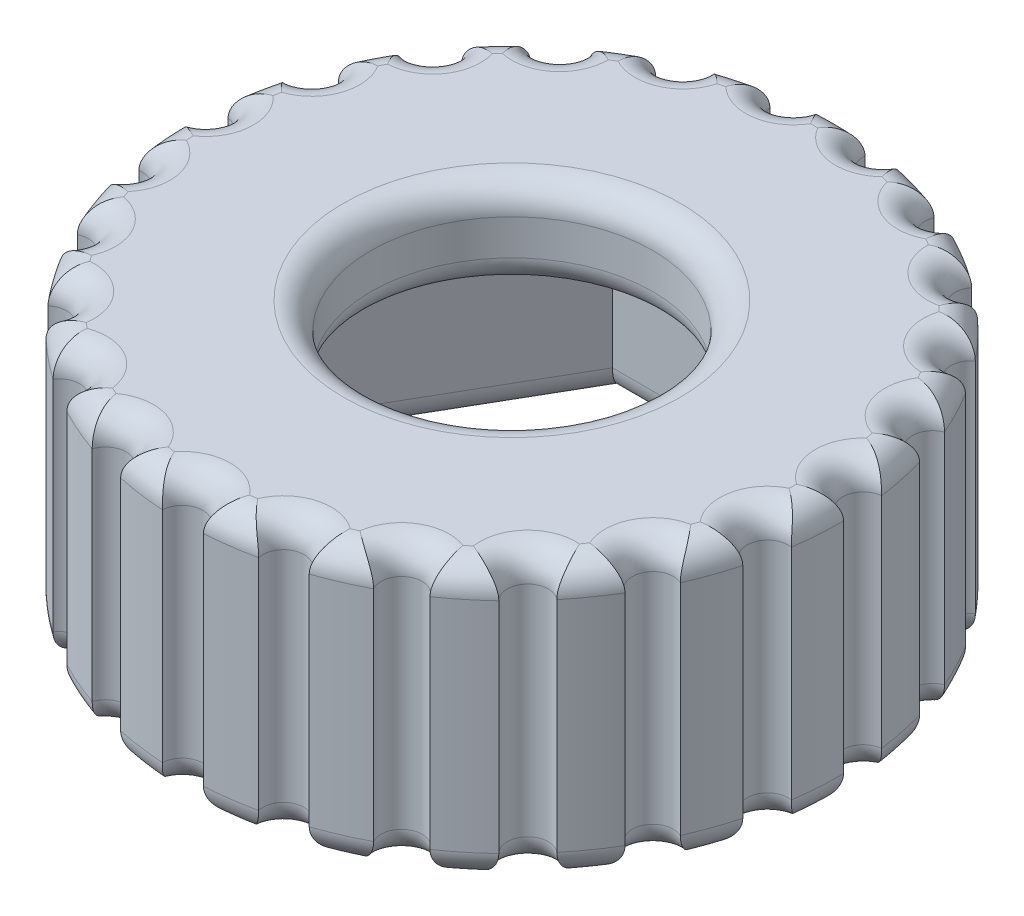
SolidWorks part; units mm, degrees
ref_plane "Front Plane" through (0, 0, 0) normal (0, 0, 1) x (1, 0, 0)
ref_plane "Top Plane" through (0, 0, 0) normal (0, 1, 0) x (1, 0, 0)
ref_plane "Right Plane" through (0, 0, 0) normal (1, 0, 0) x (0, 0, -1)
sketch "Sketch1" plane through (0, 0, 0) normal (0, 1, 0) x (1, 0, 0)
  line L0 (10.0459, 0) -> (5.0229, 8.7)
  line L1 (5.0229, 8.7) -> (-5.0229, 8.7)
  line L2 (-5.0229, 8.7) -> (-10.0459, 0)
  line L3 (-10.0459, 0) -> (-5.0229, -8.7)
  line L4 (-5.0229, -8.7) -> (5.0229, -8.7)
  line L5 (5.0229, -8.7) -> (10.0459, 0)
  line L6 (9.815, 0) -> (4.9075, 8.5) construction
  line L7 (4.9075, 8.5) -> (-4.9075, 8.5) construction
  line L8 (-4.9075, 8.5) -> (-9.815, 0) construction
  line L9 (-9.815, 0) -> (-4.9075, -8.5) construction
  line L10 (-4.9075, -8.5) -> (4.9075, -8.5) construction
  line L11 (4.9075, -8.5) -> (9.815, 0) construction
  circle A0 centre (0, 0) radius 10.0459 construction
  circle A1 centre (0, 0) radius 12.0459
extrude "Boss-Extrude1" add sketch "Sketch1" along normal blind 10
sketch "Sketch2" plane through (0, 10, 0) normal (0, 1, 0) x (1, 0, 0)
  circle A0 centre (0, 0) radius 5 construction
  circle A1 centre (0, 0) radius 12.0459
  circle A2 centre (0, 0) radius 12.0459
  circle A3 centre (0, 0) radius 5.15
  dimension "D2" = 10
  dimension "D1" = 0
  dimension "D3" = 0.15
extrude "Boss-Extrude2" add sketch "Sketch2" against normal blind 3.3
fillet "Fillet1" radius 1 7 edges at (0, 6.7, 5.15) (7.5344, 6.7, -4.35) (0, 6.7, -8.7) (-7.5344, 6.7, -4.35) (-7.5344, 6.7, 4.35) (0, 6.7, 8.7) (7.5344, 6.7, 4.35)
sketch "Sketch3" plane through (0, 0, 0) normal (0, -1, 0) x (1, 0, 0)
  circle A0 centre (0, 12.0459) radius 0.75
  circle A1 centre (0, 0) radius 12.0459 construction
  point P4 (0, 0)
  dimension "D1" = 1.5
extrude "Cut-Extrude1" cut sketch "Sketch3" against normal through all both and the other way through all
pattern_circular "CirPattern1" count 23 over 360 about axis through (0, 0, 0) along (0, 1, 0) of "Cut-Extrude1"
fillet "Fillet2" radius 1 99 edges at (0, 10, 5.15) (-10.6437, 10, -3.7828) (-9.2284, 10, -6.5141) (-7.1287, 10, -8.7624) (-4.5003, 10, -10.3607) (-1.5381, 10, -11.1907) (1.5381, 10, -11.1907) (4.5003, 10, -10.3607) (7.1287, 10, -8.7624) (9.2284, 10, -6.5141) (10.6437, 10, -3.7828) (11.2696, 10, -0.7709) (11.0596, 10, 2.2982) (10.0295, 10, 5.1968) (8.2554, 10, 7.71) (5.8692, 10, 9.6514) (3.0476, 10, 10.877) (0, 10, 11.2959) (-3.0476, 10, 10.877) (-5.8692, 10, 9.6514) (-8.2554, 10, 7.71) (-10.0295, 10, 5.1968) (-11.0596, 10, 2.2982) (-11.2696, 10, -0.7709) (0, 0, 8.7) (-7.5344, 0, 4.35) (-7.5344, 0, -4.35) (0, 0, -8.7) (7.5344, 0, -4.35) (7.5344, 0, 4.35) (-11.0596, 0, 2.2982) (-10.0295, 0, 5.1968) (-8.2554, 0, 7.71) (-5.8692, 0, 9.6514) (-3.0476, 0, 10.877) (0, 0, 11.2959) (3.0476, 0, 10.877) (5.8692, 0, 9.6514) (8.2554, 0, 7.71) (10.0295, 0, 5.1968) (11.0596, 0, 2.2982) (11.2696, 0, -0.7709) (10.6437, 0, -3.7828) (9.2284, 0, -6.5141) (7.1287, 0, -8.7624) (4.5003, 0, -10.3607) (1.5381, 0, -11.1907) (-1.5381, 0, -11.1907) (-4.5003, 0, -10.3607) (-7.1287, 0, -8.7624) (-9.2284, 0, -6.5141) (-10.6437, 0, -3.7828) (-11.2696, 0, -0.7709) (-11.7939, 10, -2.4508) (-10.6954, 10, -5.5419) (-8.8036, 10, -8.222) (-6.2589, 10, -10.2922) (-3.2499, 10, -11.5992) (0, 10, -12.0459) (3.2499, 10, -11.5992) (6.2589, 10, -10.2922) (8.8036, 10, -8.222) (10.6954, 10, -5.5419) (11.7939, 10, -2.4508) (12.0178, 10, 0.822) (11.3504, 10, 4.0339) (9.8411, 10, 6.9466) (7.602, 10, 9.3441) (4.7991, 10, 11.0486) (1.6402, 10, 11.9337) (-1.6402, 10, 11.9337) (-4.7991, 10, 11.0486) (-7.602, 10, 9.3441) (-9.8411, 10, 6.9466) (-11.3504, 10, 4.0339) (-12.0178, 10, 0.822) (-11.3504, 0, 4.0339) (-9.8411, 0, 6.9466) (-7.602, 0, 9.3441) (-4.7991, 0, 11.0486) (-1.6402, 0, 11.9337) (1.6402, 0, 11.9337) (4.7991, 0, 11.0486) (7.602, 0, 9.3441) (9.8411, 0, 6.9466) (11.3504, 0, 4.0339) (12.0178, 0, 0.822) (11.7939, 0, -2.4508) (10.6954, 0, -5.5419) (8.8036, 0, -8.222) (6.2589, 0, -10.2922) (3.2499, 0, -11.5992) (0, 0, -12.0459) (-3.2499, 0, -11.5992) (-6.2589, 0, -10.2922) (-8.8036, 0, -8.222) (-10.6954, 0, -5.5419) (-11.7939, 0, -2.4508) (-12.0178, 0, 0.822)
